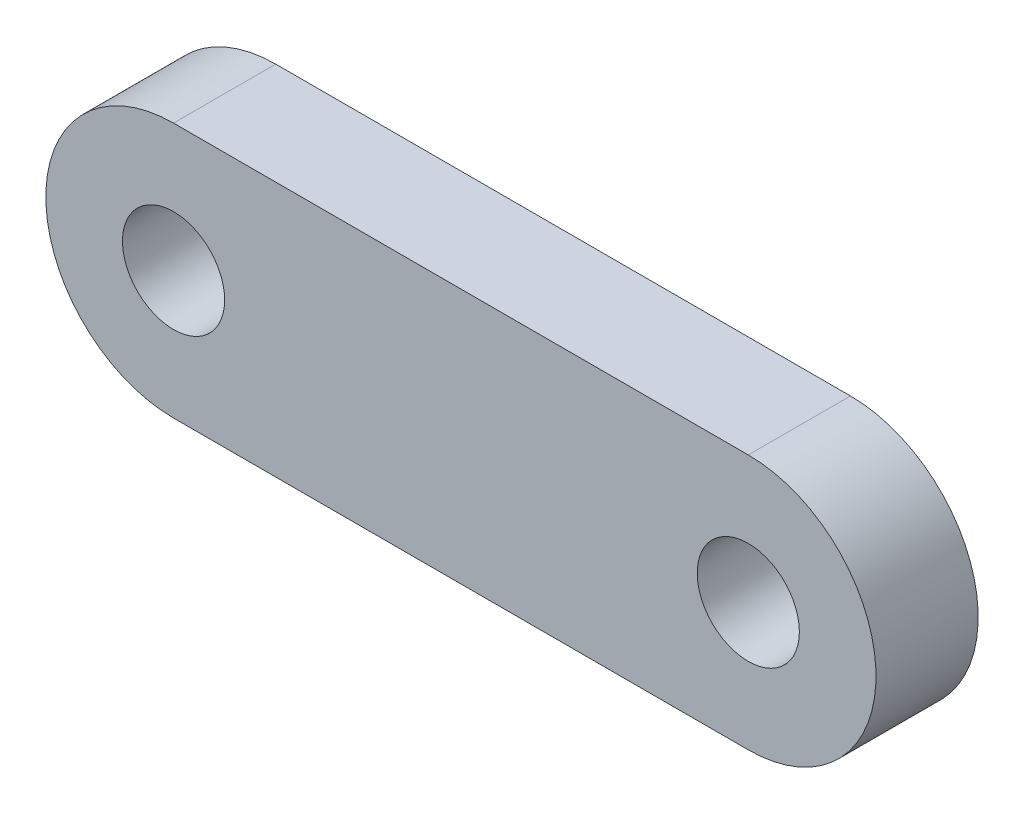
SolidWorks part; units mm, degrees
material "ABS"
ref_plane "Front Plane" through (0, 0, 0) normal (0, 0, 1) x (1, 0, 0)
ref_plane "Top Plane" through (0, 0, 0) normal (0, 1, 0) x (1, 0, 0)
ref_plane "Right Plane" through (0, 0, 0) normal (1, 0, 0) x (0, 0, -1)
sketch "Sketch1" plane through (0, 0, 0) normal (0, 0, 1) x (1, 0, 0)
  line L0 (0, 3.175) -> (14.2875, 3.175)
  line L1 (0, -3.175) -> (14.2875, -3.175)
  circle A0 centre (0, 0) radius 1.27
  circle A1 centre (0, 0) radius 3.175
  circle A2 centre (14.2875, 0) radius 1.27
  circle A3 centre (14.2875, 0) radius 3.175
  dimension "D1" = 2.54
  dimension "D2" = 6.35
  dimension "D3" = 14.2875
extrude "Boss-Extrude1" add sketch "Sketch1" along normal blind 2.54 contours A3 L0 A1 L1 | A1 A0 | A3 A2 region at (7.1437, 0, 0) region at (2.1816, 2.1816, 0) region at (16.4691, 2.1816, 0)
